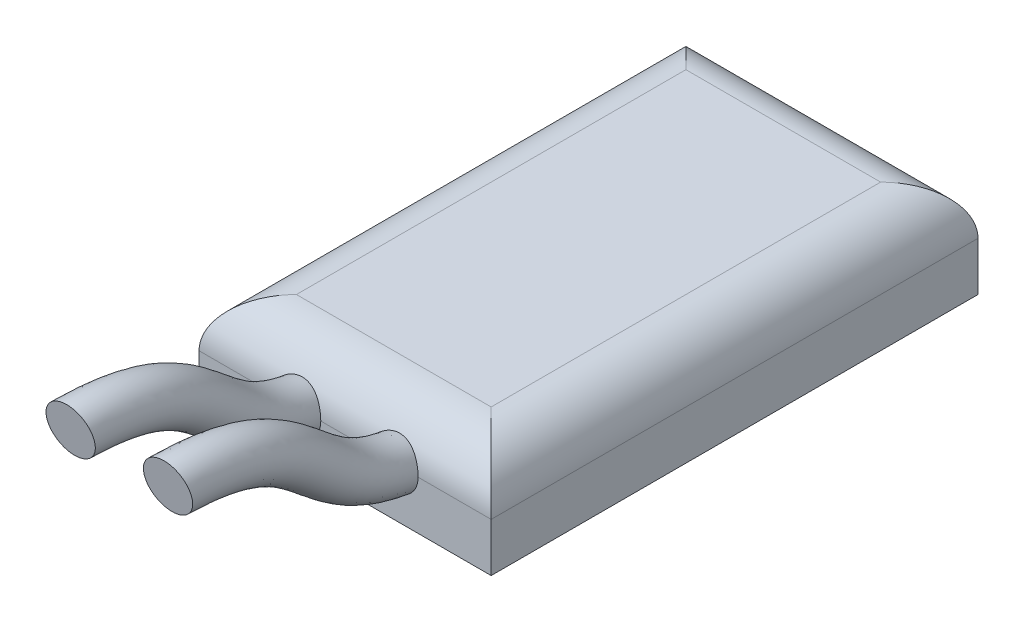
SolidWorks part; units mm, degrees
ref_plane "Front Plane" through (0, 0, 0) normal (0, 0, 1) x (1, 0, 0)
ref_plane "Top Plane" through (0, 0, 0) normal (0, 1, 0) x (1, 0, 0)
ref_plane "Right Plane" through (0, 0, 0) normal (1, 0, 0) x (0, 0, -1)
sketch "Sketch1" plane through (0, 0, 0) normal (0, 0, 1) x (1, 0, 0)
  line L1 (0, 0) -> (3, 0)
  line L2 (0, 0) -> (0, 1)
  line L3 (0, 1) -> (3, 1)
  line L4 (3, 0) -> (3, 1)
  dimension "D1" = 1
  dimension "D2" = 3
extrude "Boss-Extrude1" add sketch "Sketch1" along normal blind 5
sketch "Sketch2" plane through (0, 0, 5) normal (0, 0, 1) x (1, 0, 0)
  line L0 (0, 0.5) -> (3, 0.5) construction
  line L1 (0, 1) -> (0, 0) construction
  line L2 (3, 0) -> (3, 1) construction
  circle A0 centre (1, 0.5) radius 0.25
  circle A1 centre (2, 0.5) radius 0.25
  point P6 (1.5, 0.5)
  point P7 (2, 0.5)
  point P8 (1, 0.5)
  dimension "D3" = 0.5
  dimension "D1" = 0.5
  dimension "D2" = 0.5
ref_plane "Plane1" through (1, 0, 0) normal (-1, 0, 0) x (0, 0, 1)
sketch "Sketch3" plane through (1, 0, 0) normal (-1, 0, 0) x (0, 0, 1)
  spline S0 degree 3 poles (4.3406, 0.4689) (6.0625, 0.3757) (5.6104, 1.4296) (7.3187, 1.4548) knots 0 0 0 0 1 1 1 1
  point P2 (0, 0)
  point P3 (7.3187, 1.4548)
  point P4 (6.4625, 1.1372)
  point P6 (7.3569, 1.2254)
  point P7 (5.7644, 0.8687)
sweep "Sweep1" add profiles "Sketch2" path "Sketch3"
fillet "Fillet1" radius 0.5 4 edges at (3, 1, 2.5) (1.5, 1, 5) (0, 1, 2.5) (1.5, 1, 0)
